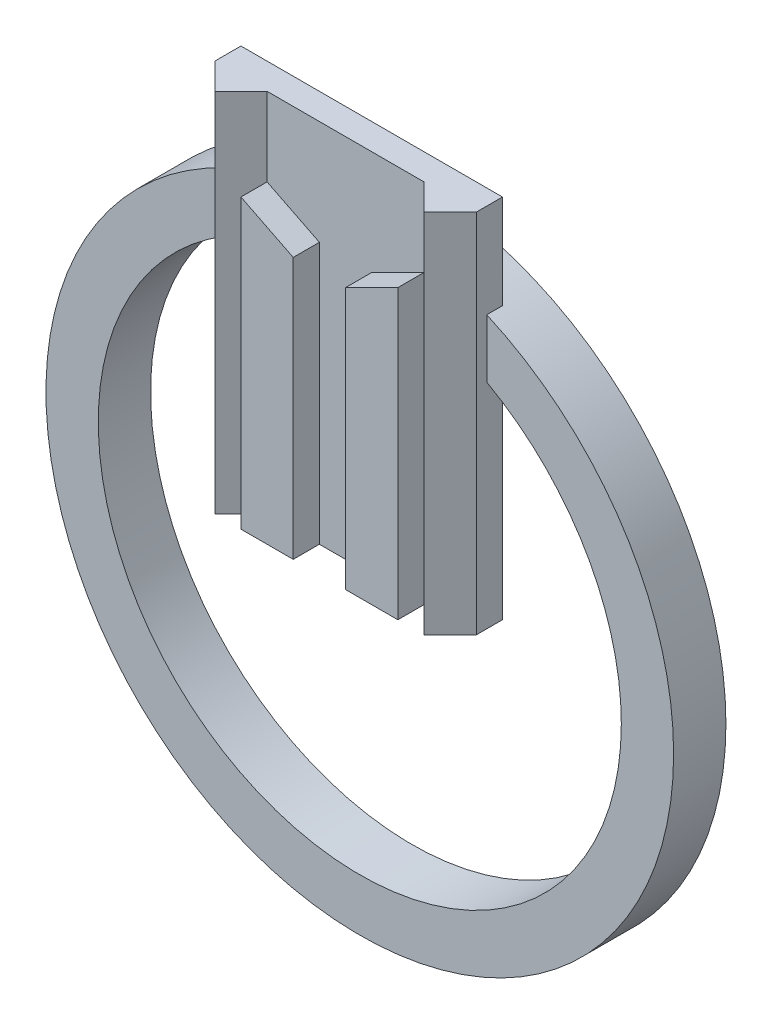
SolidWorks part; units mm, degrees
ref_plane "Front Plane" through (0, 0, 0) normal (0, 0, 1) x (1, 0, 0)
ref_plane "Top Plane" through (0, 0, 0) normal (0, 1, 0) x (1, 0, 0)
ref_plane "Right Plane" through (0, 0, 0) normal (1, 0, 0) x (0, 0, -1)
sketch "Sketch1" plane through (0, 0, 0) normal (0, 0, 1) x (1, 0, 0)
  line L1 (-25, 35) -> (25, 35)
  line L2 (-25, 35) -> (-25, -35)
  line L3 (-25, -35) -> (25, -35)
  line L4 (25, 35) -> (25, -35)
  line L5 (-25, 35) -> (25, -35) construction
  line L6 (-25, -35) -> (25, 35) construction
  point P0 (0, 0)
  dimension "D1" = 70
  dimension "D2" = 50
extrude "Boss-Extrude1" add sketch "Sketch1" along normal blind 5
sketch "Sketch2" plane through (0, 0, 5) normal (0, 0, 1) x (1, 0, 0)
  line L0 (-25, -35) -> (25, -35) construction
  line L1 (-25, 35) -> (-15, 35)
  line L2 (-25, 35) -> (-25, -35)
  line L3 (-25, -35) -> (-15, -35)
  line L4 (-15, 35) -> (-15, -35)
  line L6 (25, 35) -> (15, 35)
  line L7 (25, 35) -> (25, -35)
  line L8 (25, -35) -> (15, -35)
  line L9 (15, 35) -> (15, -35)
  dimension "D1" = 10
  dimension "D2" = 10
extrude "Boss-Extrude2" add sketch "Sketch2" along normal blind 10
chamfer "Chamfer1" distance 10 angle 45 2 edges at (-15, 0, 15) (-25, 0, 15)
chamfer "Chamfer2" distance 10 angle 45 2 edges at (25, 0, 15) (15, 0, 15)
sketch "Sketch3" plane through (0, 0, 5) normal (0, 0, 1) x (1, 0, 0)
  line L0 (-15, -35) -> (15, -35) construction
  line L2 (-5, -35) -> (-5, 15)
  line L4 (5, -35) -> (5, 15)
  line L5 (25, 35) -> (25, -35) construction
  line L6 (15, 20) -> (-15, 20) construction
  line L7 (-15, -35) -> (-15, 35) construction
  line L8 (15, 35) -> (-15, 35) construction
  line L9 (-5, 15) -> (-15, 20)
  line L10 (5, 15) -> (15, 20)
  line L11 (-15, 20) -> (-15, -35)
  line L12 (-15, -35) -> (-5, -35)
  line L13 (15, 20) -> (15, -35)
  line L14 (15, 35) -> (15, -35) construction
  line L15 (15, -35) -> (5, -35)
  point P14 (0, 20)
  dimension "D1" = 20
  dimension "D2" = 20
  dimension "D3" = 50
  dimension "D4" = 15
extrude "Boss-Extrude3" add sketch "Sketch3" along normal blind 5
sketch "Sketch7" plane through (0, 0, 0) normal (0, 0, 1) x (1, 0, 0)
  circle A0 centre (0.7244, -37.8671) radius 60
  circle A1 centre (0.7244, -37.8671) radius 50
  dimension "D1" = 120
extrude "Boss-Extrude5" add sketch "Sketch7" along normal blind 3 and the other way blind 7
